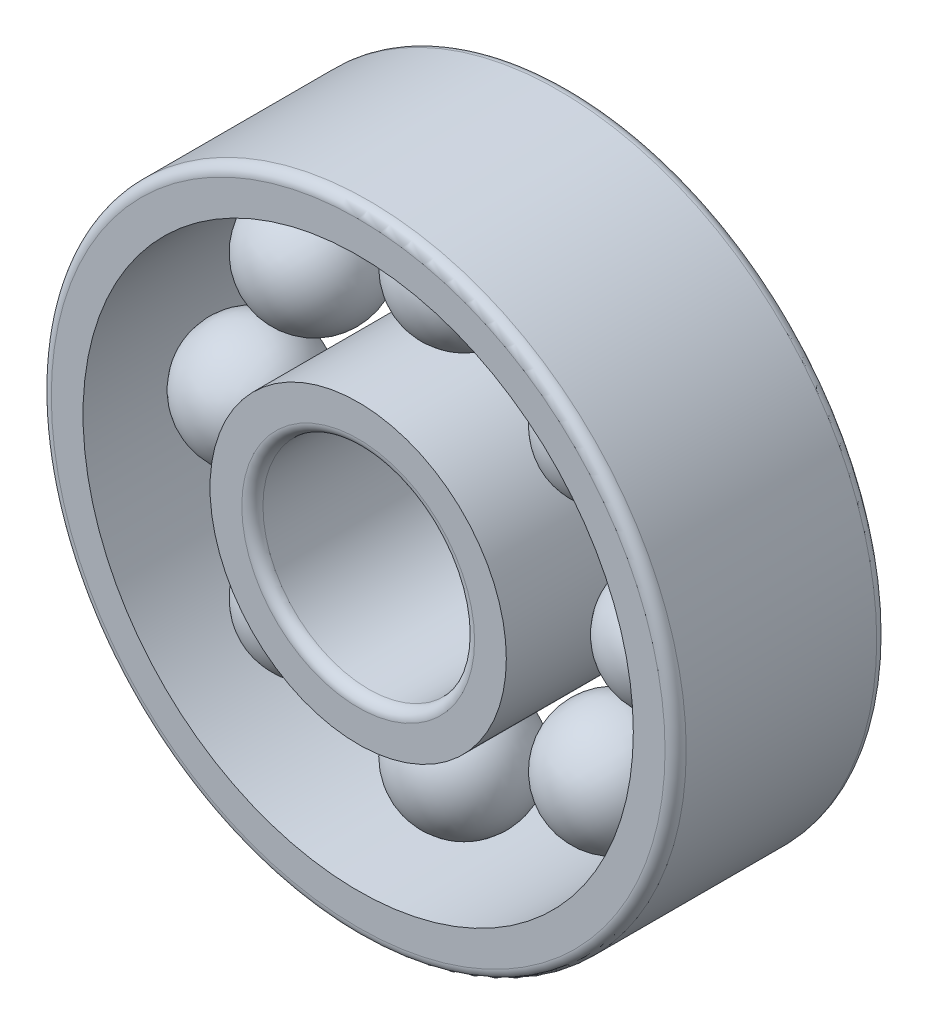
SolidWorks part; units mm, degrees
ref_plane "Front Plane" through (0, 0, 0) normal (0, 0, 1) x (1, 0, 0)
ref_plane "Top Plane" through (0, 0, 0) normal (0, 1, 0) x (1, 0, 0)
ref_plane "Right Plane" through (0, 0, 0) normal (1, 0, 0) x (0, 0, -1)
sketch "S" plane through (0, 0, 0) normal (0, 0, 1) x (1, 0, 0)
  line L0 (-0.5, 0) -> (0.5, 0) construction
  circle A0 centre (0, 0) radius 0.5 construction
  circle A1 centre (0, 0) radius 1.5 construction
  circle A2 centre (0, 0) radius 0.7 construction
  circle A3 centre (0, 0) radius 1.3 construction
  dimension "ID" = 1
  dimension "OD" = 3
  dimension "IDa" = 1.4
  dimension "ODa" = 2.6
  dimension "B" = 1
ref_axis "Z" through (0, 0, -0.55) along (0, 0, 1)
sketch "InnerS" plane through (0, 0, 0) normal (0, 1, 0) x (1, 0, 0)
  line L0 (0.5, -0.5) -> (0.7, -0.5)
  line L1 (0.7, -0.5) -> (0.7, 0.5)
  line L2 (0.7, 0.5) -> (0.5, 0.5)
  line L3 (0.5, 0.5) -> (0.5, -0.5)
  line L4 (0, -1.75) -> (0, 1.75) construction
  dimension "r1" = 0.5
  dimension "r2" = 0.7
  dimension "z1" = 0.5
  dimension "z2" = 0.5
revolve "InnerRing" add sketch "InnerS" angle 360 about L4
sketch "OuterS" plane through (0, 0, 0) normal (0, 1, 0) x (1, 0, 0)
  line L0 (1.3, -0.5) -> (1.5, -0.5)
  line L1 (1.5, -0.5) -> (1.5, 0.5)
  line L2 (1.5, 0.5) -> (1.3, 0.5)
  line L3 (1.3, 0.5) -> (1.3, -0.5)
  line L4 (0, -1.75) -> (0, 1.75) construction
  dimension "r1" = 1.3
  dimension "r2" = 1.5
  dimension "z1" = 0.5
  dimension "z2" = 0.5
revolve "OuterRing" add sketch "OuterS" angle 360 about L4
sketch "BallS" plane through (0, 0, 0) normal (0, 1, 0) x (1, 0, 0)
  line L0 (0.715, 0) -> (1.285, 0)
  arc A0 (0.715, 0) -> (1.285, 0) centre (1, 0) ccw
  dimension "r" = 0.285
  dimension "p" = 1
revolve "Ball" add sketch "BallS" angle 360 about L0
pattern_circular "BallsPattern" count 8 over 360 about axis through (0, 0, -0.55) along (0, 0, 1) of bodies 103
fillet "F1" radius 0.05 2 edges at (1.5, 0, -0.5) (1.5, 0, 0.5)
fillet "F2" radius 0.05 2 edges at (0.5, 0, -0.5) (0.5, 0, 0.5)
equation "\"r1@InnerS\" = abs(0.5*\"ID@S\")"
equation "\"r2@InnerS\" = abs(0.5*\"IDa@S\")"
equation "\"z1@InnerS\" = abs(-0.5*\"B@S\")"
equation "\"z2@InnerS\" = abs(0.5*\"B@S\")"
equation "\"r1@OuterS\" = abs(0.5*\"ODa@S\")"
equation "\"r2@OuterS\" = abs(0.5*\"OD@S\")"
equation "\"z1@OuterS\" = abs(-0.5*\"B@S\")"
equation "\"z2@OuterS\" = abs(0.5*\"B@S\")"
equation "\"r@BallS\" = abs(0.2375*\"ODa@S\"-0.2375*\"IDa@S\")"
equation "\"p@BallS\" = abs(0.25*\"IDa@S\"+0.25*\"ODa@S\")"
equation "\"N@BallsPattern\" = int(2.417*(0.25*\"IDa@S\"+0.25*\"ODa@S\")/(0.2375*\"ODa@S\"-0.2375*\"IDa@S\"))"
equation "\"r_min@F2\" = \"r_min@F1\""
